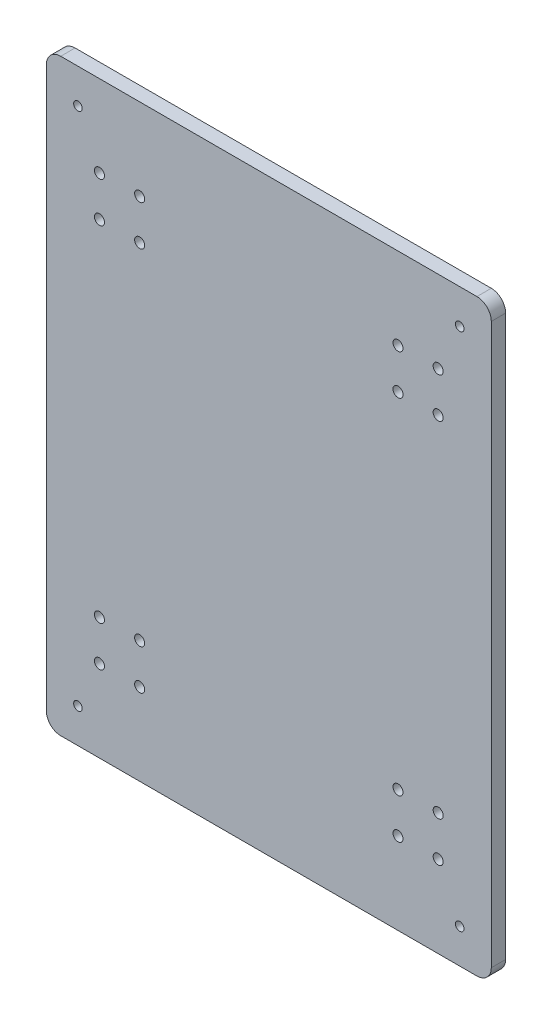
SolidWorks part; units mm, degrees
material "6063-O"
ref_plane "正面" through (0, 0, 0) normal (0, 0, 1) x (1, 0, 0)
ref_plane "平面" through (0, 0, 0) normal (0, 1, 0) x (1, 0, 0)
ref_plane "右側面" through (0, 0, 0) normal (1, 0, 0) x (0, 0, -1)
sketch "ｽｹｯﾁ1" plane through (0, 0, 0) normal (0, 0, 1) x (1, 0, 0)
  line L1 (-77.5, 102.5) -> (77.5, 102.5)
  line L2 (-77.5, 102.5) -> (-77.5, -102.5)
  line L3 (-77.5, -102.5) -> (77.5, -102.5)
  line L4 (77.5, 102.5) -> (77.5, -102.5)
  line L5 (-77.5, 102.5) -> (77.5, -102.5) construction
  line L6 (-77.5, -102.5) -> (77.5, 102.5) construction
  point P0 (0, 0)
  dimension "D1" = 155
  dimension "D2" = 205
extrude "ﾎﾞｽ - 押し出し1" add sketch "ｽｹｯﾁ1" along normal blind 5
sketch "ｽｹｯﾁ2" plane through (0, 0, 5) normal (0, 0, 1) x (1, 0, 0)
  line L0 (45, 74) -> (45, 60) construction
  line L1 (45, 60) -> (59, 60) construction
  line L2 (59, 60) -> (59, 74) construction
  line L3 (59, 74) -> (45, 74) construction
  circle A0 centre (45, 74) radius 1.75
  circle A1 centre (59, 74) radius 1.75
  circle A2 centre (45, 60) radius 1.75
  circle A3 centre (59, 60) radius 1.75
  dimension "D5" = 3.5
  dimension "D6" = 3.5
  dimension "D7" = 3.5
  dimension "D8" = 3.5
  dimension "D1" = 14
  dimension "D2" = 14
  dimension "D3" = 45
  dimension "D4" = 60
extrude "ｶｯﾄ - 押し出し1" cut sketch "ｽｹｯﾁ2" against normal through all
mirror "ﾐﾗｰ1" about plane through (0, 0, 0) normal (0, 1, 0) of "ｶｯﾄ - 押し出し1"
mirror "ﾐﾗｰ2" about plane through (0, 0, 0) normal (1, 0, 0) of "ﾐﾗｰ1"
fillet "ﾌｨﾚｯﾄ1" radius 5 4 edges at (-77.5, -102.5, 2.5) (77.5, -102.5, 2.5) (77.5, 102.5, 2.5) (-77.5, 102.5, 2.5)
sketch "ｽｹｯﾁ3" plane through (0, 0, 5) normal (0, 0, 1) x (1, 0, 0)
  line L1 (-66.5, 90.5) -> (66.5, 90.5)
  line L2 (-66.5, 90.5) -> (-66.5, -90.5)
  line L3 (-66.5, -90.5) -> (66.5, -90.5)
  line L4 (66.5, 90.5) -> (66.5, -90.5)
  line L5 (-66.5, 90.5) -> (66.5, -90.5) construction
  line L6 (-66.5, -90.5) -> (66.5, 90.5) construction
  circle A0 centre (-66.5, 90.5) radius 1.5
  circle A1 centre (66.5, 90.5) radius 1.5
  circle A2 centre (-66.5, -90.5) radius 1.5
  circle A3 centre (66.5, -90.5) radius 1.5
  point P0 (0, 0)
  dimension "D3" = 3
  dimension "D4" = 3
  dimension "D5" = 3
  dimension "D6" = 3
  dimension "D1" = 133
  dimension "D2" = 181
extrude "ｶｯﾄ - 押し出し2" cut sketch "ｽｹｯﾁ3" against normal through all both contours A0 | A1 | A2 | A3
